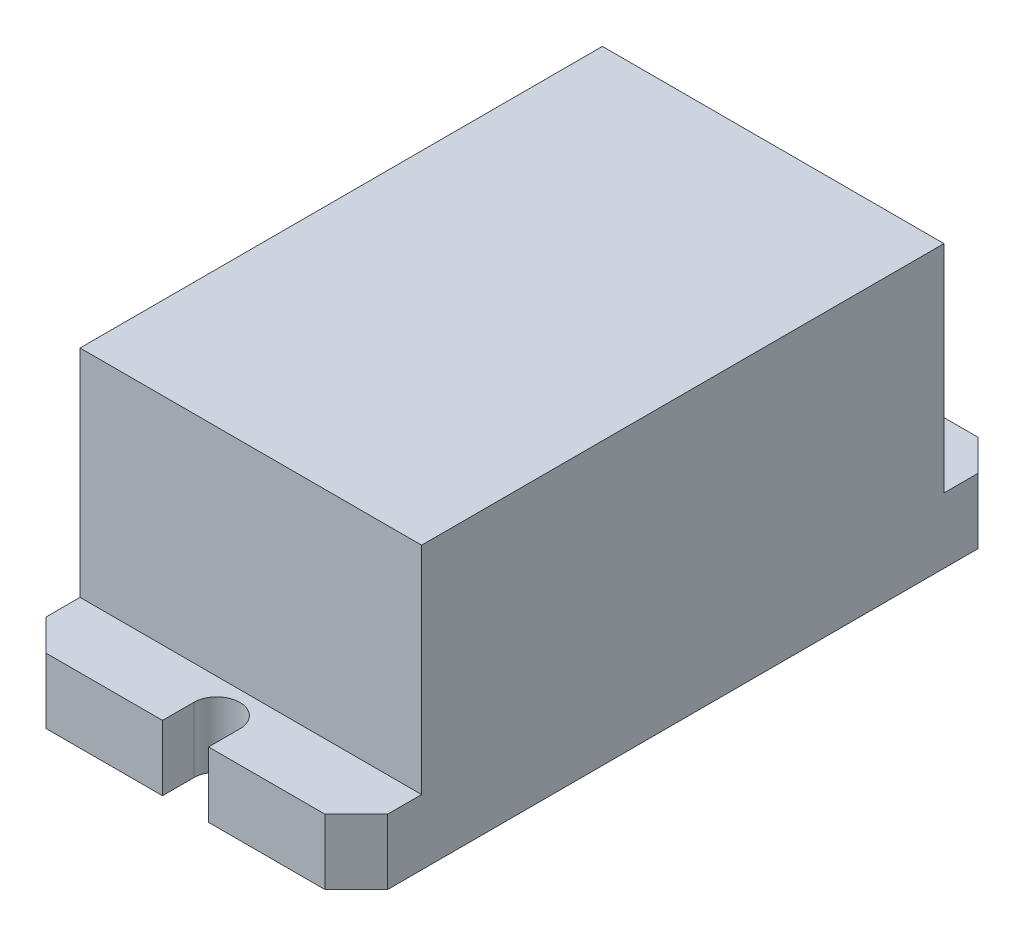
SolidWorks part; units mm, degrees
ref_plane "Front" through (0, 0, 0) normal (0, 0, 1) x (1, 0, 0)
ref_plane "Top" through (0, 0, 0) normal (0, 1, 0) x (1, 0, 0)
ref_plane "Right" through (0, 0, 0) normal (1, 0, 0) x (0, 0, -1)
sketch "Sketch1" plane through (0, 0, 0) normal (0, 1, 0) x (1, 0, 0)
  line L0 (0, 0) -> (-21.59, 0)
  line L1 (-21.59, 0) -> (-21.59, 33.02)
  line L2 (-21.59, 33.02) -> (-21.59, 37.3238)
  line L3 (-21.59, 37.3238) -> (-17.6388, 41.275)
  line L4 (-17.6388, 41.275) -> (-2.9098, 41.275)
  line L5 (-2.9098, 41.275) -> (-2.9098, 37.3238)
  line L6 (-2.9098, 37.3238) -> (0, 37.3238) construction
  line L7 (0, 80.7729) -> (0, 0) construction
  line L8 (0, 0) -> (-111.7864, 0) construction
  line L10 (-21.59, 33.02) -> (0, 33.02)
  line L11 (0, 0) -> (0, 33.02)
  line L12 (0, 33.02) -> (0, 34.4141)
  arc A0 (-2.9098, 37.3238) -> (0, 34.4141) centre (0, 37.3238) ccw
  point P12 (-49.5979, 41.275)
  point P16 (0, 35.447)
  point P17 (0, 34.0561)
  point P18 (0, 0)
  point P19 (0, 35.501)
  point P20 (-2.9098, 41.275)
  dimension "D1" = 33.02
  dimension "D2" = 45
  dimension "D3" = 8.255
  dimension "D4" = 21.59
extrude "Boss-Extrude1" add sketch "Sketch1" along normal blind 35.56 contours L0 L11 L10 L1 region at (-10.795, 0, -16.51)
extrude "Boss-Extrude2" add sketch "Sketch1<3>" along normal blind 8.255 contours A0 L5 L4 L3 L2 L10 L12 region at (-11.4318, 0, -36.8872)
sketch "Sketch1<3>" plane through (0, 0, 0) normal (0, 1, 0) x (1, 0, 0) same geometry as "Sketch1"
mirror "Mirror1" about plane through (0, 35.56, 0) normal (0, 0, 1) of bodies 102
mirror "Mirror2" about plane through (0, 35.56, 0) normal (-1, 0, 0) of bodies 103
